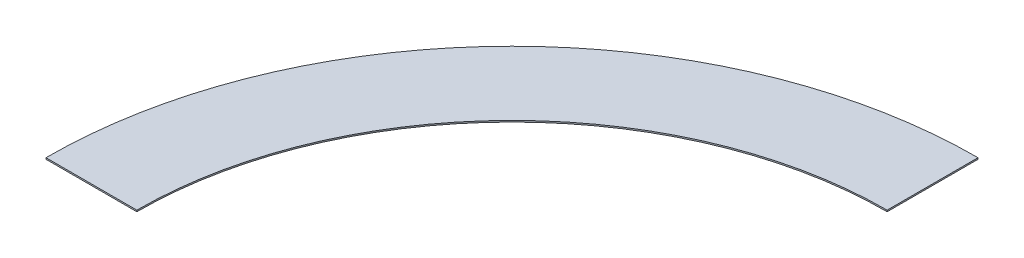
SolidWorks part; units mm, degrees
note: The reader was unsure of these and kept them because the rebuilt part matched: thickness of "基体-法兰1", "钣金3".
material "普通碳钢"
ref_plane "前视基准面" through (0, 0, 0) normal (0, 0, 1) x (1, 0, 0)
ref_plane "上视基准面" through (0, 0, 0) normal (0, 1, 0) x (1, 0, 0)
ref_plane "右视基准面" through (0, 0, 0) normal (1, 0, 0) x (0, 0, -1)
ref_plane "基准面2" through (0, 2989, 0) normal (0, 1, 0) x (1, 0, 0)
ref_plane "基准面1" [suppressed] through (0, 3532, 0) normal (0, 1, 0) x (1, 0, 0)
sketch "草图1" plane through (0, 2989, 0) normal (0, 1, 0) x (1, 0, 0)
  line L0 (0, 0) -> (0, 969.5) construction
  line L1 (0, 0) -> (-969.5, 0) construction
  line L3 (-780.5, 0) -> (-969.5, 0)
  line L4 (0, 969.5) -> (0, 780.5)
  circle A0 centre (0, 0) radius 969.5 construction
  arc A1 (-969.5, 0) -> (0, 969.5) centre (0, 0) cw
  circle A2 centre (0, 0) radius 780.5 construction
  arc A3 (-780.5, 0) -> (0, 780.5) centre (0, 0) cw
  dimension "D1" = 1939
  dimension "D2" = 189
sketch "草图2" [suppressed] plane through (0, 3532, 0) normal (0, 1, 0) x (1, 0, 0)
  line L0 (0, 0) -> (0, 561) construction
  line L1 (0, 0) -> (-561, 0) construction
  circle A0 centre (0, 0) radius 561 construction
  arc A1 (-561, 0) -> (0, 561) centre (0, 0) cw
  dimension "D1" = 1122
base flange "基体-法兰1" sketch "草图1" thickness 3 reverse thickness direction no parameters "D1"=8
sketch "草图5" plane through (0, 2989, 0) normal (0, 1, 0) x (1, 0, 0)
  line L0 (-200.79, 1170.29) -> (-1170.29, 200.79)
  line L5 (-200.79, 1170.29) -> (94.5, 875)
  line L6 (-1170.29, 200.79) -> (-875, -94.5)
  line L7 (94.5, 875) -> (-875, -94.5)
  arc A1 (0, 969.5) -> (-969.5, 0) centre (0, 0) ccw construction
  dimension "D1" = 417.6032
  dimension "D2" = 1371.08
sketch "折弯-线1" plane through (0, 0, 0) normal (0, 1, 0) x (1, 0, 0)
sketch "边界框1" plane through (0, 0, 0) normal (0, 1, 0) x (1, 0, 0)
sheet metal parameters "钣金3" thickness 3 parameters "D1"=8
flat pattern "平板型式3" [suppressed]
sketch "折弯-线2" plane through (0, 0, 0) normal (0, 1, 0) x (1, 0, 0)
sketch "边界框2" [suppressed] plane through (0, 0, 0) normal (0, 1, 0) x (1, 0, 0)
